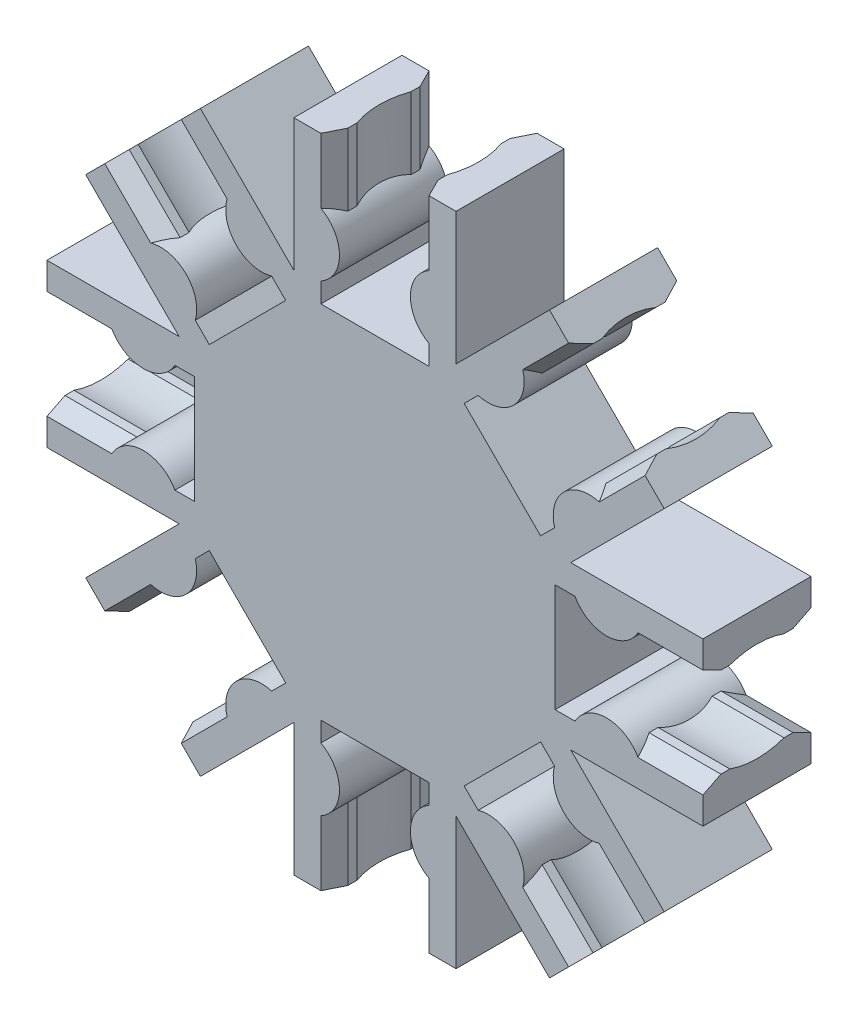
SolidWorks part; units mm, degrees
ref_plane "前视基准面" through (0, 0, 0) normal (0, 0, 1) x (1, 0, 0)
ref_plane "上视基准面" through (0, 0, 0) normal (0, 1, 0) x (1, 0, 0)
ref_plane "右视基准面" through (0, 0, 0) normal (1, 0, 0) x (0, 0, -1)
sketch "草图1" plane through (0, 0, 0) normal (0, 0, 1) x (1, 0, 0)
  line L0 (-4.5, 0) -> (-4.5, -18.2)
  line L1 (4.5, 0) -> (4.5, -18.2)
  line L2 (-4.5, -18.2) -> (-3, -18.2)
  line L3 (-3, -18.2) -> (-3, -14.6)
  line L4 (4.5, -18.2) -> (3, -18.2)
  line L5 (3, -18.2) -> (3, -14.6)
  line L6 (-3, -11.1) -> (-3, -10)
  line L7 (-3, -10) -> (3, -10)
  line L8 (3, -10) -> (3, -11.1)
  arc A0 (4.5, 0) -> (-4.5, 0) centre (0, 0) ccw
  arc A1 (-3, -11.1) -> (-3, -14.6) centre (-3.9682, -12.85) cw
  arc A2 (3, -11.1) -> (3, -14.6) centre (3.9682, -12.85) ccw
  point P1 (0, 4.5)
  dimension "D1" = 9
  dimension "D10" = 14.5
  dimension "D11" = 2
  dimension "D12" = 2
  dimension "D2" = 18.2
  dimension "D3" = 18.2
  dimension "D4" = 1.5
  dimension "D5" = 1.5
  dimension "D6" = 1.1
  dimension "D7" = 1.1
  dimension "D8" = 3.5
  dimension "D9" = 3.5
extrude "凸台-拉伸1" add sketch "草图1" along normal blind 6
sketch "草图3" plane through (0, -18.2, 0) normal (0, -1, 0) x (1, 0, 0)
  line L0 (-3, 6) -> (-3, 0)
  line L1 (-3, 0) -> (-2.5, 1)
  line L2 (-2.5, 1) -> (-2.5, 1.5)
  line L3 (-3, 6) -> (-2.5, 5)
  line L4 (-2.5, 5) -> (-2.5, 4.5)
  line L5 (0, 0) -> (0, 6.4845) construction
  line L6 (3, 0) -> (2.5, 1)
  line L7 (2.5, 1) -> (2.5, 1.5)
  line L8 (2.5, 5) -> (2.5, 4.5)
  line L9 (3, 6) -> (2.5, 5)
  line L10 (3, 6) -> (3, 0)
  arc A0 (-2.5, 1.5) -> (-2.5, 4.5) centre (1.7426, 3) cw
  arc A1 (2.5, 1.5) -> (2.5, 4.5) centre (-1.7426, 3) ccw
  dimension "D7" = 4.5
  dimension "D1" = 0.5
  dimension "D2" = 0.5
  dimension "D3" = 0.5
  dimension "D4" = 0.5
  dimension "D5" = 1.5
  dimension "D6" = 1.5
extrude "凸台-拉伸2" add sketch "草图3" against normal up to next
ref_axis "Axis" through (0, 0, 0) along (0, 0, 1)
pattern_circular "阵列(圆周)1" count 8 every 45 about axis through (0, 0, 0) along (0, 0, 1) of "凸台-拉伸1", "凸台-拉伸2"
sketch "草图4" plane through (0, 0, 0) normal (0, 0, -1) x (-1, 0, 0)
  line L0 (0, 0) -> (-4.5, -10.864) construction
  line L1 (0, 0) -> (4.5, -10.864) construction
  line L2 (0, 0) -> (0, -10) construction
  line L3 (3, -10) -> (-3, -10) construction
  line L4 (-3, -8.75) -> (3, -8.75)
  line L5 (-3, -8.75) -> (-1.1749, -4.3439)
  line L6 (3, -8.75) -> (1.1749, -4.3439)
  line L7 (-8.3085, -4.0659) -> (-3.9024, -2.2408)
  line L8 (-8.3085, -4.0659) -> (-4.0659, -8.3085)
  line L9 (-4.0659, -8.3085) -> (-2.2408, -3.9024)
  line L10 (-8.75, 3) -> (-4.3439, 1.1749)
  line L11 (-8.75, 3) -> (-8.75, -3)
  line L12 (-8.75, -3) -> (-4.3439, -1.1749)
  line L13 (-4.0659, 8.3085) -> (-2.2408, 3.9024)
  line L14 (-4.0659, 8.3085) -> (-8.3085, 4.0659)
  line L15 (-8.3085, 4.0659) -> (-3.9024, 2.2408)
  line L16 (3, 8.75) -> (1.1749, 4.3439)
  line L17 (3, 8.75) -> (-3, 8.75)
  line L18 (-3, 8.75) -> (-1.1749, 4.3439)
  line L19 (8.3085, 4.0659) -> (3.9024, 2.2408)
  line L20 (8.3085, 4.0659) -> (4.0659, 8.3085)
  line L21 (4.0659, 8.3085) -> (2.2408, 3.9024)
  line L22 (8.75, -3) -> (4.3439, -1.1749)
  line L23 (8.75, -3) -> (8.75, 3)
  line L24 (8.75, 3) -> (4.3439, 1.1749)
  line L25 (4.0659, -8.3085) -> (2.2408, -3.9024)
  line L26 (4.0659, -8.3085) -> (8.3085, -4.0659)
  line L27 (8.3085, -4.0659) -> (3.9024, -2.2408)
  circle A0 centre (0, 0) radius 3
  arc A1 (-2.2408, 3.9024) -> (-3.9024, 2.2408) centre (0, 0) ccw
  arc A2 (1.1749, 4.3439) -> (-1.1749, 4.3439) centre (0, 0) ccw
  arc A3 (3.9024, 2.2408) -> (2.2408, 3.9024) centre (0, 0) ccw
  arc A4 (4.3439, -1.1749) -> (4.3439, 1.1749) centre (0, 0) ccw
  arc A5 (2.2408, -3.9024) -> (3.9024, -2.2408) centre (0, 0) ccw
  arc A6 (-1.1749, -4.3439) -> (1.1749, -4.3439) centre (0, 0) ccw
  arc A7 (-3.9024, -2.2408) -> (-2.2408, -3.9024) centre (0, 0) ccw
  arc A8 (-4.3439, 1.1749) -> (-4.3439, -1.1749) centre (0, 0) ccw
  point P11 (0, -8.75)
  point P47 (0, 0)
  dimension "D3" = 9
  dimension "D4" = 6
  dimension "D1" = 6
  dimension "D2" = 1.25
  dimension "D5" = 8
